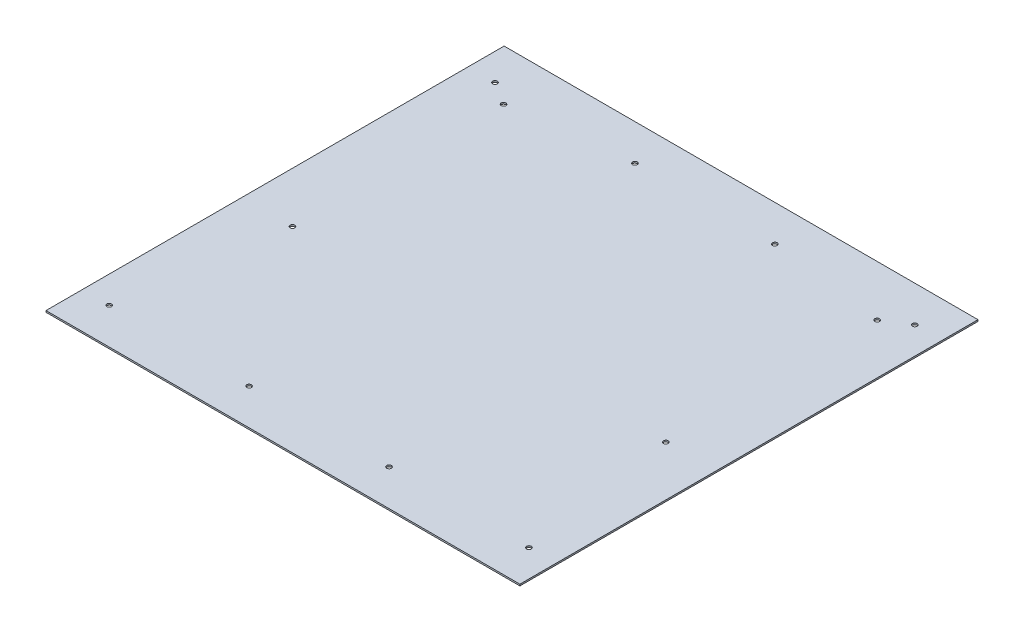
SolidWorks part; units mm, degrees
ref_plane "Front Plane" through (0, 0, 0) normal (0, 0, 1) x (1, 0, 0)
ref_plane "Top Plane" through (0, 0, 0) normal (0, 1, 0) x (1, 0, 0)
ref_plane "Right Plane" through (0, 0, 0) normal (1, 0, 0) x (0, 0, -1)
sketch "Sketch1" plane through (0, 0, 0) normal (0, 1, 0) x (1, 0, 0)
  line L1 (0, 0) -> (300, 0)
  line L2 (0, 0) -> (0, -290)
  line L3 (0, -290) -> (300, -290)
  line L4 (300, 0) -> (300, -290)
  dimension "D1" = 290
  dimension "D2" = 300
base flange "Base-Flange1" sketch "Sketch1" thickness 1 reverse thickness direction no parameters "D1"=0.7366
sketch "Sketch7" plane through (0, -1, 0) normal (0, -1, 0) x (1, 0, 0)
  circle A8 centre (17.1317, 267.1317) radius 1.5
  circle A9 centre (105.7106, 267.1317) radius 1.5
  circle A10 centre (194.2894, 267.1317) radius 1.5
  circle A11 centre (282.8683, 267.1317) radius 1.5
  circle A12 centre (282.8683, 22.8683) radius 1.5
  circle A13 centre (194.2894, 22.8683) radius 1.5
  circle A14 centre (105.7106, 22.8683) radius 1.5
  circle A15 centre (17.1317, 22.8683) radius 1.5
extrude "Cut-Extrude1" cut sketch "Sketch7" against normal up to surface (1 mm away) normal cut yes up to face at (150, 0, 145)
sketch "Sketch9" plane through (0, 0, 0) normal (0, 1, 0) x (1, 0, 0)
  circle A0 centre (31.763, -32.1322) radius 1.5
  circle A1 centre (31.941, -165.9392) radius 1.5
  circle A2 centre (268.313, -165.9392) radius 1.5
  circle A3 centre (268.313, -32.1322) radius 1.5
extrude "Cut-Extrude3" cut sketch "Sketch9" against normal through all normal cut yes
sketch "Bend-Lines1" [suppressed] plane through (0, 0, 0) normal (0, 1, 0) x (1, 0, 0)
sketch "Bounding-Box1" [suppressed] plane through (0, 0, 0) normal (0, 1, 0) x (1, 0, 0)
sheet metal parameters "Sheet-Metal1" thickness 1 parameters "D1"=0.7366
flat pattern "Flat-Pattern1" [suppressed]
sketch "Bend-Lines2" plane through (0, 0, 0) normal (0, 1, 0) x (1, 0, 0)
sketch3d "Bounding-Box2" [suppressed]
  line L0 (300, -230, 0) -> (0, -230, 0) construction
  line L1 (300, 0, 0) -> (0, 0, 0) construction
  line L2 (300, -230, 0) -> (300, 0, 0) construction
  line L3 (0, -230, 0) -> (0, 0, 0) construction
sheet metal parameters "Sheet-Metal2" thickness 1 parameters "D1"=0.7366
flat pattern "Flat-Pattern1"
sketch "Bend-Lines2" plane through (0, 0, 0) normal (0, 1, 0) x (1, 0, 0)
sketch3d "Bounding-Box2" [suppressed]
  line L0 (300, -230, 0) -> (0, -230, 0) construction
  line L1 (300, 0, 0) -> (0, 0, 0) construction
  line L2 (300, -230, 0) -> (300, 0, 0) construction
  line L3 (0, -230, 0) -> (0, 0, 0) construction
sheet metal parameters "Sheet-Metal4" thickness 1 parameters "D1"=0.7366
flat pattern "Flat-Pattern1"
sketch "Bend-Lines2" plane through (0, 0, 0) normal (0, 1, 0) x (1, 0, 0)
sketch3d "Bounding-Box2" [suppressed]
  line L0 (300, -290, 0) -> (0, -290, 0) construction
  line L1 (300, 0, 0) -> (0, 0, 0) construction
  line L2 (300, -290, 0) -> (300, 0, 0) construction
  line L3 (0, -290, 0) -> (0, 0, 0) construction
